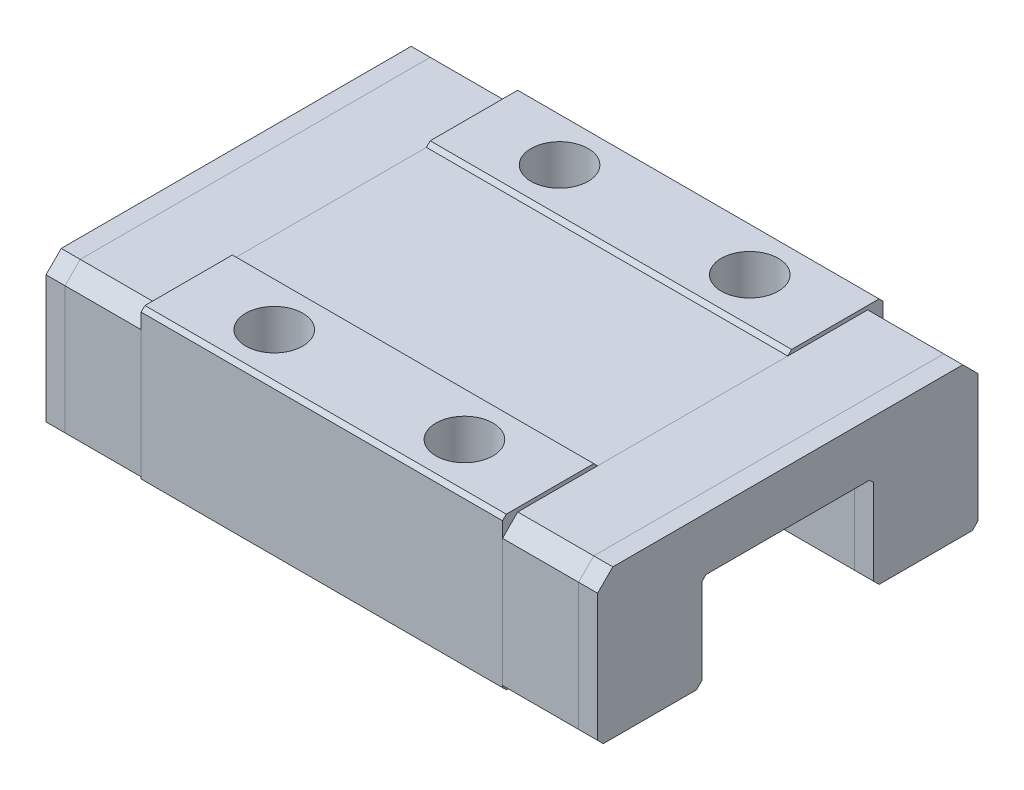
SolidWorks part; units mm, degrees
ref_plane "前视基准面" through (0, 0, 0) normal (0, 0, 1) x (1, 0, 0)
ref_plane "上视基准面" through (0, 0, 0) normal (0, 1, 0) x (1, 0, 0)
ref_plane "右视基准面" through (0, 0, 0) normal (1, 0, 0) x (0, 0, -1)
other "Configuration Table"
sketch "草图1" plane through (0, 0, 0) normal (0, 1, 0) x (1, 0, 0)
  line L1 (-9.5, 10) -> (9.5, 10)
  line L2 (-9.5, 10) -> (-9.5, -10)
  line L3 (-9.5, -10) -> (9.5, -10)
  line L4 (9.5, 10) -> (9.5, -10)
  line L5 (-9.5, 10) -> (9.5, -10) construction
  line L6 (-9.5, -10) -> (9.5, 10) construction
  point P0 (0, 0)
extrude "凸台-拉伸1" add sketch "草图1" against normal blind 8
sketch "草图2" plane through (0, 0, 0) normal (0, 1, 0) x (1, 0, 0)
  line L0 (9.5, -10) -> (9.5, 10) construction
  line L1 (-9.5, -5) -> (9.5, -5)
  line L2 (-9.5, -5) -> (-9.5, 5)
  line L3 (-9.5, 5) -> (9.5, 5)
  line L4 (9.5, -5) -> (9.5, 5)
  line L5 (-9.5, -5) -> (9.5, 5) construction
  line L6 (-9.5, 5) -> (9.5, -5) construction
  point P0 (0, 0)
  point P8 (0, 0)
extrude "切除-拉伸1" cut sketch "草图2" against normal blind 0.2
chamfer "倒角1" distance 0.2 angle 45 6 edges at (0, -8, 10) (0, -8, -10) (0, 0, -10) (0, 0, 10) (0, 0, 5) (0, 0, -5)
sketch "草图3" plane through (0, 0, 0) normal (0, 1, 0) x (1, 0, 0)
  line L1 (-5, -7.5) -> (5, -7.5) construction
  line L2 (-5, -7.5) -> (-5, 7.5) construction
  line L3 (-5, 7.5) -> (5, 7.5) construction
  line L4 (5, -7.5) -> (5, 7.5) construction
  line L5 (-5, -7.5) -> (5, 7.5) construction
  line L6 (-5, 7.5) -> (5, -7.5) construction
  circle A0 centre (-5, 7.5) radius 1.5
  circle A1 centre (5, 7.5) radius 1.5
  circle A2 centre (5, -7.5) radius 1.5
  circle A3 centre (-5, -7.5) radius 1.5
  point P0 (0, 0)
extrude "切除-拉伸2" cut sketch "草图3" against normal blind 6
sketch "草图4" plane through (9.5, 0, 0) normal (1, 0, 0) x (0, 0, -1)
  line L0 (-5, -8) -> (-5, -3)
  line L1 (-9.8, -8) -> (9.8, -8) construction
  line L2 (-5, -3) -> (5, -3)
  line L3 (5, -3) -> (5, -8)
  line L4 (5, -8) -> (-5, -8)
  point P6 (0, 0)
  point P7 (0, 0)
  point P8 (0, 0)
  point P9 (0, 0)
extrude "切除-拉伸3" cut sketch "草图4" against normal up to surface (19 mm away) up to face at (-9.5, -2.7, 0)
chamfer "倒角2" distance 0.2 angle 45 4 edges at (0, -3, -5) (0, -8, -5) (0, -8, 5) (0, -3, 5)
sketch "草图5" plane through (9.5, 0, 0) normal (1, 0, 0) x (0, 0, -1)
  line L0 (-10, -0.2) -> (10, -0.2)
  line L1 (10, -7.8) -> (10, -0.2) construction
  line L2 (10, -0.2) -> (10, -8)
  line L3 (10, -8) -> (4.5, -8)
  line L4 (4.5, -8) -> (4.5, -3)
  line L5 (4.8, -3) -> (-4.8, -3) construction
  line L6 (4.5, -3) -> (-4.5, -3)
  line L7 (-4.5, -3) -> (-4.5, -8)
  line L8 (-4.5, -8) -> (-10, -8)
  line L9 (-10, -8) -> (-10, -0.2)
extrude "凸台-拉伸2" add sketch "草图5" along normal blind 4 separate body
chamfer "倒角3" distance 0.2 angle 45 2 edges at (11.5, -3, -4.5) (11.5, -3, 4.5)
chamfer "倒角4" distance 0.3 angle 45 4 edges at (11.5, -8, 10) (11.5, -8, -10) (11.5, -8, -4.5) (11.5, -8, 4.5)
chamfer "倒角5" distance 0.8 angle 45 2 edges at (11.5, -0.2, 10) (11.5, -0.2, -10)
sketch "草图6" plane through (-9.5, 0, 0) normal (-1, 0, 0) x (0, 0, 1)
  line L16 (9.2, -0.2) -> (-9.2, -0.2)
  line L17 (10, -1) -> (9.2, -0.2)
  line L18 (10, -7.7) -> (10, -1)
  line L19 (9.7, -8) -> (10, -7.7)
  line L20 (4.8, -8) -> (9.7, -8)
  line L21 (4.5, -7.7) -> (4.8, -8)
  line L22 (4.5, -3.2) -> (4.5, -7.7)
  line L23 (4.3, -3) -> (4.5, -3.2)
  line L24 (-4.3, -3) -> (4.3, -3)
  line L25 (-4.5, -3.2) -> (-4.3, -3)
  line L26 (-4.5, -7.7) -> (-4.5, -3.2)
  line L27 (-4.8, -8) -> (-4.5, -7.7)
  line L28 (-9.7, -8) -> (-4.8, -8)
  line L29 (-10, -7.7) -> (-9.7, -8)
  line L30 (-10, -1) -> (-10, -7.7)
  line L31 (-9.2, -0.2) -> (-10, -1)
  line L32 (9.2, -0.2) -> (-9.2, -0.2)
  line L33 (10, -1) -> (9.2, -0.2)
  line L34 (10, -7.7) -> (10, -1)
  line L35 (9.7, -8) -> (10, -7.7)
  line L36 (4.8, -8) -> (9.7, -8)
  line L37 (4.5, -7.7) -> (4.8, -8)
  line L38 (4.5, -3.2) -> (4.5, -7.7)
  line L39 (4.3, -3) -> (4.5, -3.2)
  line L40 (-4.3, -3) -> (4.3, -3)
  line L41 (-4.5, -3.2) -> (-4.3, -3)
  line L42 (-4.5, -7.7) -> (-4.5, -3.2)
  line L43 (-4.8, -8) -> (-4.5, -7.7)
  line L44 (-9.7, -8) -> (-4.8, -8)
  line L45 (-10, -7.7) -> (-9.7, -8)
  line L46 (-10, -1) -> (-10, -7.7)
  line L47 (-9.2, -0.2) -> (-10, -1)
  dimension "D1" = 0
extrude "凸台-拉伸3" add sketch "草图6" along normal blind 4 separate body
sketch "草图7" plane through (-13.5, 0, 0) normal (-1, 0, 0) x (0, 0, 1)
  line L16 (-9.2, -0.2) -> (-10, -1)
  line L17 (-10, -1) -> (-10, -7.7)
  line L18 (-10, -7.7) -> (-9.7, -8)
  line L19 (-9.7, -8) -> (-4.8, -8)
  line L20 (-4.8, -8) -> (-4.5, -7.7)
  line L21 (-4.5, -7.7) -> (-4.5, -3.2)
  line L22 (-4.5, -3.2) -> (-4.3, -3)
  line L23 (-4.3, -3) -> (4.3, -3)
  line L24 (4.3, -3) -> (4.5, -3.2)
  line L25 (4.5, -3.2) -> (4.5, -7.7)
  line L26 (4.5, -7.7) -> (4.8, -8)
  line L27 (4.8, -8) -> (9.7, -8)
  line L28 (9.7, -8) -> (10, -7.7)
  line L29 (10, -7.7) -> (10, -1)
  line L30 (10, -1) -> (9.2, -0.2)
  line L31 (9.2, -0.2) -> (-9.2, -0.2)
  line L32 (-9.2, -0.2) -> (-10, -1)
  line L33 (-10, -1) -> (-10, -7.7)
  line L34 (-10, -7.7) -> (-9.7, -8)
  line L35 (-9.7, -8) -> (-4.8, -8)
  line L36 (-4.8, -8) -> (-4.5, -7.7)
  line L37 (-4.5, -7.7) -> (-4.5, -3.2)
  line L38 (-4.5, -3.2) -> (-4.3, -3)
  line L39 (-4.3, -3) -> (4.3, -3)
  line L40 (4.3, -3) -> (4.5, -3.2)
  line L41 (4.5, -3.2) -> (4.5, -7.7)
  line L42 (4.5, -7.7) -> (4.8, -8)
  line L43 (4.8, -8) -> (9.7, -8)
  line L44 (9.7, -8) -> (10, -7.7)
  line L45 (10, -7.7) -> (10, -1)
  line L46 (10, -1) -> (9.2, -0.2)
  line L47 (9.2, -0.2) -> (-9.2, -0.2)
  dimension "D1" = 0
extrude "凸台-拉伸4" add sketch "草图7" along normal blind 1 separate body
sketch "草图8" plane through (13.5, 0, 0) normal (1, 0, 0) x (0, 0, -1)
  line L16 (9.2, -0.2) -> (-9.2, -0.2)
  line L17 (-9.2, -0.2) -> (-10, -1)
  line L18 (-10, -1) -> (-10, -7.7)
  line L19 (-10, -7.7) -> (-9.7, -8)
  line L20 (-9.7, -8) -> (-4.8, -8)
  line L21 (-4.8, -8) -> (-4.5, -7.7)
  line L22 (-4.5, -7.7) -> (-4.5, -3.2)
  line L23 (-4.5, -3.2) -> (-4.3, -3)
  line L24 (-4.3, -3) -> (4.3, -3)
  line L25 (4.3, -3) -> (4.5, -3.2)
  line L26 (4.5, -3.2) -> (4.5, -7.7)
  line L27 (4.5, -7.7) -> (4.8, -8)
  line L28 (4.8, -8) -> (9.7, -8)
  line L29 (9.7, -8) -> (10, -7.7)
  line L30 (10, -7.7) -> (10, -1)
  line L31 (10, -1) -> (9.2, -0.2)
  line L32 (9.2, -0.2) -> (-9.2, -0.2)
  line L33 (-9.2, -0.2) -> (-10, -1)
  line L34 (-10, -1) -> (-10, -7.7)
  line L35 (-10, -7.7) -> (-9.7, -8)
  line L36 (-9.7, -8) -> (-4.8, -8)
  line L37 (-4.8, -8) -> (-4.5, -7.7)
  line L38 (-4.5, -7.7) -> (-4.5, -3.2)
  line L39 (-4.5, -3.2) -> (-4.3, -3)
  line L40 (-4.3, -3) -> (4.3, -3)
  line L41 (4.3, -3) -> (4.5, -3.2)
  line L42 (4.5, -3.2) -> (4.5, -7.7)
  line L43 (4.5, -7.7) -> (4.8, -8)
  line L44 (4.8, -8) -> (9.7, -8)
  line L45 (9.7, -8) -> (10, -7.7)
  line L46 (10, -7.7) -> (10, -1)
  line L47 (10, -1) -> (9.2, -0.2)
  dimension "D1" = 0
extrude "凸台-拉伸5" add sketch "草图8" along normal blind 1 separate body
